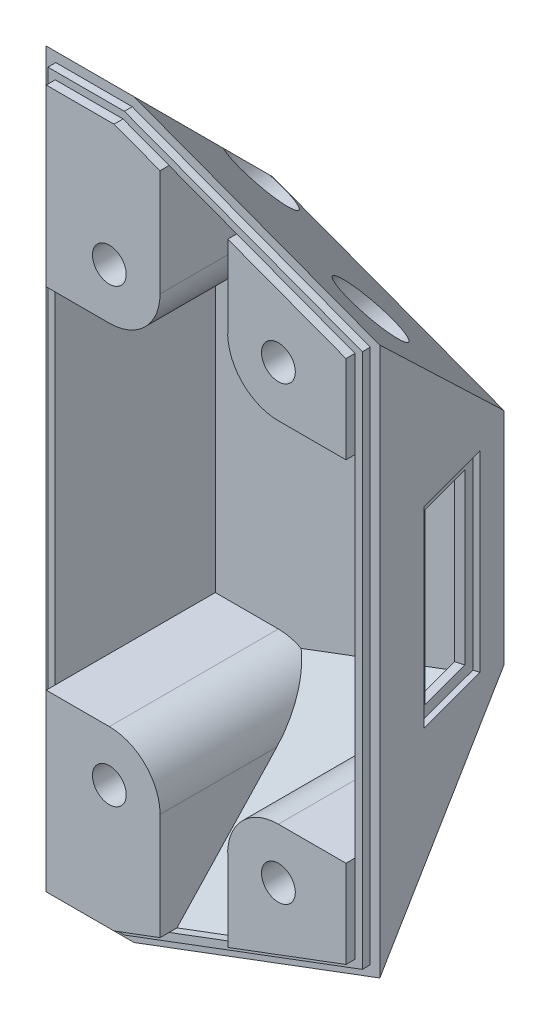
SolidWorks part; units mm, degrees
ref_plane "Front Plane" through (0, 0, 0) normal (0, 0, 1) x (1, 0, 0)
ref_plane "Top Plane" through (0, 0, 0) normal (0, 1, 0) x (1, 0, 0)
ref_plane "Right Plane" through (0, 0, 0) normal (1, 0, 0) x (0, 0, -1)
sketch "Sketch2" plane through (0, 0, 0) normal (0, 0, 1) x (1, 0, 0)
  line L0 (0, 82.55) -> (0, 0)
  line L1 (0.9525, 0.9525) -> (0.9525, 81.5975)
  line L2 (1.905, 1.905) -> (1.905, 80.645)
  line L3 (0.9525, 81.5975) -> (9.7163, 81.5975)
  line L4 (9.7163, 81.5975) -> (36.6395, 71.5013)
  line L5 (36.6395, 71.5013) -> (36.6395, 11.0487)
  line L6 (36.6395, 11.0487) -> (9.7163, 0.9525)
  line L7 (9.7163, 0.9525) -> (0.9525, 0.9525)
  line L8 (1.905, 80.645) -> (9.5436, 80.645)
  line L9 (9.5436, 80.645) -> (35.687, 70.8412)
  line L10 (35.687, 70.8412) -> (35.687, 11.7088)
  line L11 (0, 0) -> (9.8891, 0)
  line L12 (9.8891, 0) -> (37.592, 10.3886)
  line L13 (37.592, 10.3886) -> (37.592, 72.1614)
  line L14 (37.592, 72.1614) -> (9.8891, 82.55)
  line L15 (9.8891, 82.55) -> (0, 82.55)
  line L16 (35.687, 11.7088) -> (9.5436, 1.905)
  line L17 (9.5436, 1.905) -> (1.905, 1.905)
  line L18 (1.0795, 1.0795) -> (1.0795, 81.4705)
  line L19 (1.0795, 81.4705) -> (9.6933, 81.4705)
  line L20 (9.6933, 81.4705) -> (36.5125, 71.4133)
  line L21 (36.5125, 71.4133) -> (36.5125, 11.1367)
  line L22 (36.5125, 11.1367) -> (9.6933, 1.0795)
  line L23 (9.6933, 1.0795) -> (1.0795, 1.0795)
  line L34 (0.9525, 0.9525) -> (9.7163, 0.9525)
  line L35 (9.7163, 0.9525) -> (36.6395, 11.0487)
  line L36 (36.6395, 11.0487) -> (36.6395, 71.5013)
  line L37 (36.6395, 71.5013) -> (9.7163, 81.5975)
  line L38 (9.7163, 81.5975) -> (0.9525, 81.5975)
  dimension "D1" = 90
  dimension "D2" = 0.9525
  dimension "D3" = 0.9525
  dimension "D4" = 0.8255
extrude "Boss-Extrude1" add sketch "Sketch2" along normal blind 0.889 contours L23 L22 L21 L20 L19 L18 L17 region at (1.1674, 41.275, 0)
sketch "Sketch3" plane through (0, 0, 0) normal (0, 0, -1) x (-1, 0, 0)
  line L0 (0, 82.55) -> (0, 0) construction
  line L1 (0, 0) -> (-9.8891, 0) construction
  line L2 (-9.8891, 0) -> (-37.592, 10.3886) construction
  line L3 (-37.592, 10.3886) -> (-37.592, 72.1614) construction
  line L4 (-9.8891, 82.55) -> (0, 82.55) construction
  line L5 (-37.592, 72.1614) -> (-9.8891, 82.55) construction
  line L6 (0, 82.55) -> (0, 0)
  line L7 (0, 0) -> (-9.8891, 0)
  line L8 (-9.8891, 0) -> (-37.592, 10.3886)
  line L9 (-37.592, 10.3886) -> (-37.592, 72.1614)
  line L10 (-9.8891, 82.55) -> (0, 82.55)
  line L11 (-37.592, 72.1614) -> (-9.8891, 82.55)
ref_plane "Plane1" through (0, 0, -19.05) normal (0, 0, 1) x (1, 0, 0)
sketch "Sketch4" plane through (0, 0, -19.05) normal (0, 0, 1) x (1, 0, 0)
  line L0 (9.8891, 82.55) -> (0, 82.55) construction
  line L1 (37.592, 72.1614) -> (9.8891, 82.55) construction
  line L2 (37.592, 10.3886) -> (37.592, 72.1614) construction
  line L3 (9.8891, 0) -> (37.592, 10.3886) construction
  line L4 (0, 0) -> (9.8891, 0) construction
  line L5 (0, 82.55) -> (0, 0) construction
  line L26 (9.8891, 82.55) -> (0, 82.55)
  line L27 (0, 63.5) -> (0, 19.05)
  line L28 (37.592, 72.1614) -> (9.8891, 82.55)
  line L29 (37.592, 10.3886) -> (37.592, 72.1614)
  line L30 (9.8891, 0) -> (37.592, 10.3886)
  line L31 (0, 0) -> (9.8891, 0)
  line L32 (32.512, 53.721) -> (6.4346, 63.5)
  line L33 (6.4346, 63.5) -> (0, 63.5)
  line L34 (0, 19.05) -> (6.4346, 19.05)
  line L35 (6.4346, 19.05) -> (32.512, 28.829)
  line L36 (32.512, 53.721) -> (32.512, 28.829)
  line L40 (30.9031, 54.3243) -> (6.4346, 63.5) construction
  line L41 (6.4346, 19.05) -> (30.9031, 28.2257) construction
  dimension "D2" = 5.08
  dimension "D1" = 19.05
loft "Loft2" add section "Sketch4" section "Sketch2<7>"
sketch "Sketch2<7>" plane through (0, 0, 0) normal (0, 0, 1) x (1, 0, 0) same geometry as "Sketch2"
ref_plane "Plane2" through (0, 0, -17.145) normal (0, 0, 1) x (1, 0, 0)
sketch "Sketch5" plane through (0, 0, -17.145) normal (0, 0, 1) x (1, 0, 0)
  line L1 (33.02, 26.985) -> (6.7801, 17.145)
  line L2 (33.02, 26.985) -> (33.02, 55.565)
  line L3 (33.02, 26.985) -> (33.02, 55.565)
  line L4 (33.02, 26.985) -> (6.7801, 17.145)
  line L5 (6.7801, 17.145) -> (0, 17.145)
  line L6 (6.7801, 17.145) -> (0, 17.145)
  line L7 (0, 65.405) -> (0, 17.145)
  line L8 (0, 65.405) -> (0, 17.145)
  line L9 (0, 65.405) -> (6.7801, 65.405)
  line L10 (0, 65.405) -> (6.7801, 65.405)
  line L11 (6.7801, 65.405) -> (33.02, 55.565)
  line L12 (31.115, 28.3051) -> (31.115, 54.2449)
  line L13 (6.4346, 63.5) -> (31.115, 54.2449)
  line L14 (1.905, 63.5) -> (6.4346, 63.5)
  line L15 (1.905, 63.5) -> (1.905, 19.05)
  line L16 (6.4346, 19.05) -> (1.905, 19.05)
  line L17 (31.115, 28.3051) -> (6.4346, 19.05)
  line L24 (6.7801, 65.405) -> (33.02, 55.565)
  dimension "D1" = 1.905
loft "Cut-Loft1" cut section "Sketch2<8>" section "Sketch5"
sketch "Sketch2<8>" plane through (0, 0, 0) normal (0, 0, 1) x (1, 0, 0) same geometry as "Sketch2"
sketch "Sketch8" plane through (35.0963, 0, -9.359) normal (0.9662, 0, -0.2577) x (-0.2577, 0, -0.9662)
  line L0 (-9.6861, 41.275) -> (10.0296, 41.275) construction
  line L1 (4.9496, 50.8) -> (-1.4004, 50.8)
  line L2 (4.9496, 50.8) -> (4.9496, 31.75)
  line L3 (4.9496, 31.75) -> (-1.4004, 31.75)
  line L4 (-1.4004, 50.8) -> (-1.4004, 31.75)
  line L8 (10.0296, 53.721) -> (-9.6861, 72.1614)
  line L9 (-9.6861, 72.1614) -> (-9.6861, 10.3886)
  line L10 (-9.6861, 10.3886) -> (10.0296, 28.829)
  line L11 (10.0296, 28.829) -> (10.0296, 53.721)
  line L12 (10.0296, 53.721) -> (-9.6861, 72.1614)
  line L13 (-9.6861, 72.1614) -> (-9.6861, 10.3886)
  line L14 (-9.6861, 10.3886) -> (10.0296, 28.829)
  line L15 (10.0296, 28.829) -> (10.0296, 53.721)
  point P6 (10.0296, 41.275)
  point P9 (-9.6861, 41.275)
  dimension "D1" = 19.05
  dimension "D2" = 6.35
  dimension "D4" = 9.525
  dimension "D5" = 5.08
  dimension "D3" = 0
extrude "Cut-Extrude2" cut sketch "Sketch8" against normal blind 5.08 contours L0 L4 L3 L2 | L4 L0 L2 L1 region at (34.639, 46.0375, -11.0737) region at (34.639, 36.5125, -11.0737)
sketch "Sketch9" plane through (35.0963, 0, -9.359) normal (0.9662, 0, -0.2577) x (-0.2577, 0, -0.9662)
  line L8 (-2.6704, 30.48) -> (6.2196, 30.48)
  line L9 (-2.6704, 52.07) -> (-2.6704, 30.48)
  line L10 (6.2196, 30.48) -> (6.2196, 52.07)
  line L11 (6.2196, 52.07) -> (-2.6704, 52.07)
  line L12 (-2.6704, 30.48) -> (6.2196, 30.48)
  line L13 (-2.6704, 52.07) -> (-2.6704, 30.48)
  line L14 (6.2196, 30.48) -> (6.2196, 52.07)
  line L15 (6.2196, 52.07) -> (-2.6704, 52.07)
  dimension "D1" = 1.27
extrude "Cut-Extrude3" cut sketch "Sketch9" against normal blind 0.635
sketch "Sketch10" plane through (33.3177, 0, -8.8847) normal (-0.9662, 0, 0.2577) x (0.2577, 0, 0.9662)
  line L0 (-8.5489, 41.275) -> (9.1952, 41.275) construction
  line L1 (3.8134, 56.515) -> (-7.3626, 56.515)
  line L2 (3.8134, 56.515) -> (3.8134, 26.035)
  line L3 (3.8134, 26.035) -> (-7.3626, 26.035)
  line L4 (-7.3626, 56.515) -> (-7.3626, 26.035)
  line L5 (1.4004, 50.8) -> (-4.9496, 50.8) construction
  line L6 (1.4004, 50.8) -> (-4.9496, 50.8)
  line L8 (-8.5489, 28.3051) -> (9.1952, 11.7088)
  line L9 (9.1952, 11.7088) -> (9.1952, 70.8412)
  line L10 (9.1952, 70.8412) -> (-8.5489, 54.2449)
  line L11 (-8.5489, 54.2449) -> (-8.5489, 28.3051)
  line L12 (-8.5489, 28.3051) -> (9.1952, 11.7088)
  line L13 (9.1952, 11.7088) -> (9.1952, 70.8412)
  line L14 (9.1952, 70.8412) -> (-8.5489, 54.2449)
  line L15 (-8.5489, 54.2449) -> (-8.5489, 28.3051)
  point P12 (-1.7746, 50.8)
  line M9 (-8.5489, 28.3051) -> (9.1952, 11.7088)
  line M11 (9.1952, 70.8412) -> (-8.5489, 54.2449)
  line M13 (1.4004, 31.75) -> (-4.9496, 31.75)
  line M14 (-4.9496, 31.75) -> (-4.9496, 50.8)
  line M15 (-4.9496, 50.8) -> (1.4004, 50.8)
  line M16 (1.4004, 50.8) -> (1.4004, 31.75)
  dimension "D1" = 11.176
  dimension "D2" = 30.48
  dimension "D3" = 0
  dimension "D4" = 15.24
  dimension "D5" = 5.588
extrude "Cut-Extrude4" cut sketch "Sketch10" against normal blind 0.254 and the other way blind 2.54 contours L4 L0 L2 L1 M14 M15 M16 M11 | L1 L4 M11 | L0 L4 L3 L2 M9 M16 M13 M14 | L4 L3 M9 region at (31.4694, 48.3147, -15.8162) region at (31.7315, 41.086, -14.833) region at (31.5272, 56.1281, -15.5991) region at (31.5272, 26.4219, -15.5991)
ref_plane "Plane3" through (0, 0, 1.905) normal (0, 0, 1) x (1, 0, 0)
sketch "Sketch11" plane through (0, 0, 1.905) normal (0, 0, 1) x (1, 0, 0)
  line L0 (0, 82.55) -> (0, 0) construction
  line L1 (0, 82.55) -> (0, 41.275)
  line L2 (0, 41.275) -> (47.3444, 41.275) construction
  line L3 (37.592, 10.3886) -> (37.592, 72.1614) construction
  line L4 (9.017, 15.875) -> (28.067, 15.875)
  line L5 (9.017, 15.875) -> (9.017, 66.675)
  line L6 (9.017, 66.675) -> (28.067, 66.675)
  line L7 (28.067, 15.875) -> (28.067, 66.675)
  line L8 (9.017, 21.59) -> (1.905, 21.59)
  line L9 (35.687, 70.8412) -> (35.687, 11.7088) construction
  line L10 (35.687, 11.7088) -> (9.5436, 1.905) construction
  line L11 (35.687, 70.8412) -> (35.687, 41.275)
  line L12 (35.687, 11.7088) -> (9.5436, 1.905)
  line L13 (22.3628, 15.5239) -> (22.3628, 6.7122)
  line L14 (28.067, 21.59) -> (35.687, 21.59)
  line L15 (35.687, 70.8412) -> (35.687, 11.7088)
  line L16 (14.732, 15.875) -> (14.732, 3.8506)
  line L17 (1.905, 1.905) -> (1.905, 80.645) construction
  line L18 (9.5436, 1.905) -> (1.905, 1.905) construction
  line L19 (1.905, 1.905) -> (1.905, 21.59)
  line L20 (9.5436, 1.905) -> (1.905, 1.905)
  line L21 (1.905, 41.275) -> (1.905, 80.645)
  line L22 (28.067, 60.96) -> (35.687, 60.96)
  line L23 (22.3628, 67.0261) -> (22.3628, 75.8378)
  line L24 (14.732, 66.675) -> (14.732, 78.6994)
  line L25 (35.687, 70.8412) -> (9.5436, 80.645)
  line L26 (9.5436, 80.645) -> (1.905, 80.645)
  line L27 (1.905, 80.645) -> (1.905, 60.96)
  line L28 (9.017, 60.96) -> (1.905, 60.96)
  arc A0 (14.732, 15.875) -> (9.017, 21.59) centre (9.017, 15.875) ccw
  arc A1 (28.067, 21.59) -> (22.3628, 15.5239) centre (28.067, 15.875) ccw
  arc A2 (28.067, 60.96) -> (22.3628, 67.0261) centre (28.067, 66.675) cw
  arc A3 (14.732, 66.675) -> (9.017, 60.96) centre (9.017, 66.675) cw
  dimension "D2" = 19.05
  dimension "D3" = 25.4
  dimension "D4" = 9.525
extrude "Boss-Extrude2" add sketch "Sketch11" against normal up to body contours L20 L12 L16 L4 L5 L8 L19 | L4 A0 L5 | L4 A1 L13 L12 L15 L14 L7 | L7 A1 L4 | A2 L6 L7 L22 L11 L25 L23 | A2 L7 L6 | L28 L5 L6 L24 L25 L26 L21 | A3 L6 L5 region at (11.4425, 18.3005, 1.905) region at (7.6677, 10.9014, 1.905) region at (25.6415, 18.3005, 1.905) region at (29.4047, 14.4747, 1.905) region at (7.6677, 71.6486, 1.905) region at (11.4425, 64.2495, 1.905) region at (25.6415, 64.2495, 1.905) region at (29.4047, 68.0753, 1.905)
sketch "Sketch12" plane through (0, 0, -19.05) normal (0, 0, -1) x (-1, 0, 0)
  arc A0 (-22.3628, 15.5239) -> (-28.067, 21.59) centre (-28.067, 15.875) ccw construction
  arc A1 (-9.017, 21.59) -> (-14.732, 15.875) centre (-9.017, 15.875) ccw construction
  arc A2 (-14.732, 66.675) -> (-9.017, 60.96) centre (-9.017, 66.675) ccw construction
  arc A3 (-28.067, 60.96) -> (-22.3628, 67.0261) centre (-28.067, 66.675) ccw construction
  arc A4 (-22.3628, 15.5239) -> (-28.067, 21.59) centre (-28.067, 15.875) ccw
  arc A5 (-9.017, 21.59) -> (-14.732, 15.875) centre (-9.017, 15.875) ccw
  arc A6 (-14.732, 66.675) -> (-9.017, 60.96) centre (-9.017, 66.675) ccw
  arc A7 (-28.067, 60.96) -> (-22.3628, 67.0261) centre (-28.067, 66.675) ccw
  circle A8 centre (-28.067, 15.875) radius 3.81
  circle A9 centre (-9.017, 15.875) radius 3.81
  circle A10 centre (-9.017, 66.675) radius 3.81
  circle A11 centre (-28.067, 66.675) radius 3.81
extrude "Cut-Extrude5" cut sketch "Sketch12" against normal blind 16.51 contours A8 | A9 | A10 | A11 region at (28.067, 15.875, -19.05) region at (9.017, 15.875, -19.05) region at (9.017, 66.675, -19.05) region at (28.067, 66.675, -19.05)
sketch "Sketch13" plane through (0, 0, -2.54) normal (0, 0, -1) x (-1, 0, 0)
  circle A0 centre (-9.017, 66.675) radius 3.81 construction
  circle A1 centre (-28.067, 66.675) radius 3.81 construction
  circle A2 centre (-9.017, 15.875) radius 3.81 construction
  circle A3 centre (-28.067, 15.875) radius 3.81 construction
  circle A16 centre (-28.067, 15.875) radius 3.81
  circle A17 centre (-9.017, 15.875) radius 3.81
  circle A18 centre (-28.067, 66.675) radius 3.81
  circle A19 centre (-9.017, 66.675) radius 3.81
  circle A20 centre (-9.017, 15.875) radius 1.905
  circle A21 centre (-28.067, 15.875) radius 1.905
  circle A22 centre (-9.017, 66.675) radius 1.905
  circle A23 centre (-28.067, 66.675) radius 1.905
extrude "Cut-Extrude6" cut sketch "Sketch13" against normal through all contours A20 | A21 | A23 | A22 region at (9.017, 15.875, -2.54) region at (28.067, 15.875, -2.54) region at (9.017, 66.675, -2.54) region at (28.067, 66.675, -2.54)
